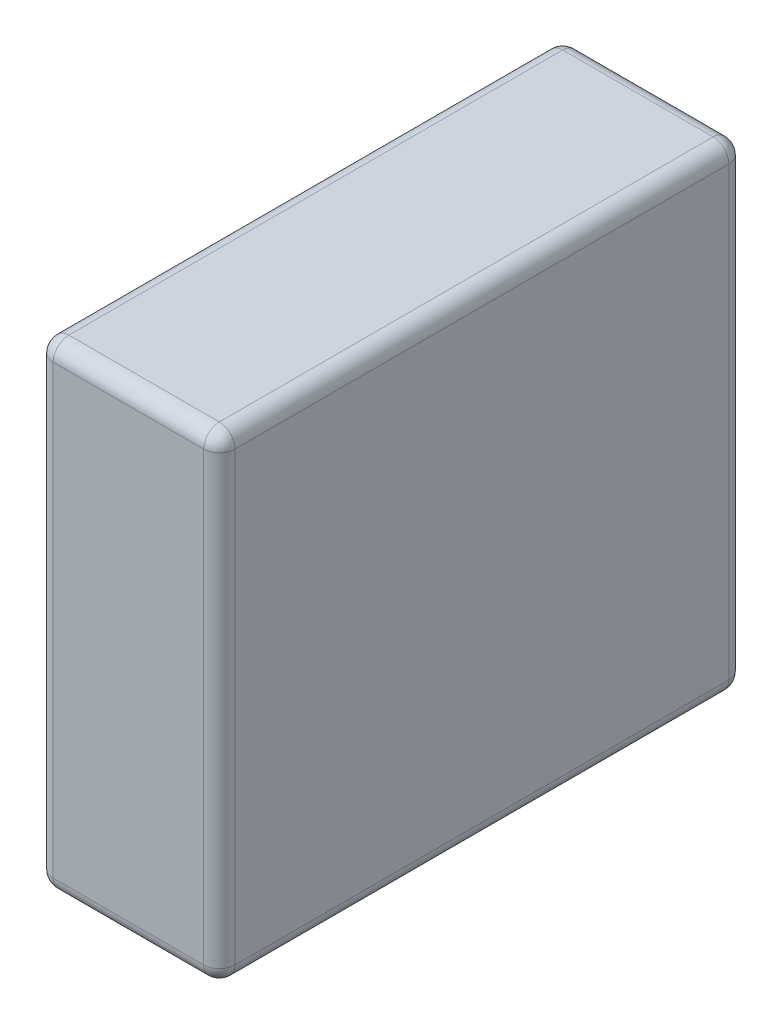
SolidWorks part; units mm, degrees
ref_plane "Спереди" through (0, 0, 0) normal (0, 0, 1) x (1, 0, 0)
ref_plane "Сверху" through (0, 0, 0) normal (0, 1, 0) x (1, 0, 0)
ref_plane "Справа" through (0, 0, 0) normal (1, 0, 0) x (0, 0, -1)
sketch "Эскиз1" plane through (0, 0, 0) normal (0, 1, 0) x (1, 0, 0)
  line L1 (-11.6, 33.5) -> (11.6, 33.5)
  line L2 (-11.6, 33.5) -> (-11.6, -33.5)
  line L3 (-11.6, -33.5) -> (11.6, -33.5)
  line L4 (11.6, 33.5) -> (11.6, -33.5)
  line L5 (-11.6, 33.5) -> (11.6, -33.5) construction
  line L6 (-11.6, -33.5) -> (11.6, 33.5) construction
  point P0 (0, 0)
  dimension "D1" = 23.2
  dimension "D2" = 67
extrude "Бобышка-Вытянуть1" add sketch "Эскиз1" along normal blind 30.5 and the other way blind 30.5
fillet "Скругление2" radius 2 12 edges at (0, -30.5, -33.5) (0, 30.5, -33.5) (-11.6, -30.5, 0) (-11.6, 0, -33.5) (-11.6, 30.5, 0) (11.6, -30.5, 0) (11.6, 30.5, 0) (11.6, 0, -33.5) (0, -30.5, 33.5) (-11.6, 0, 33.5) (0, 30.5, 33.5) (11.6, 0, 33.5)
